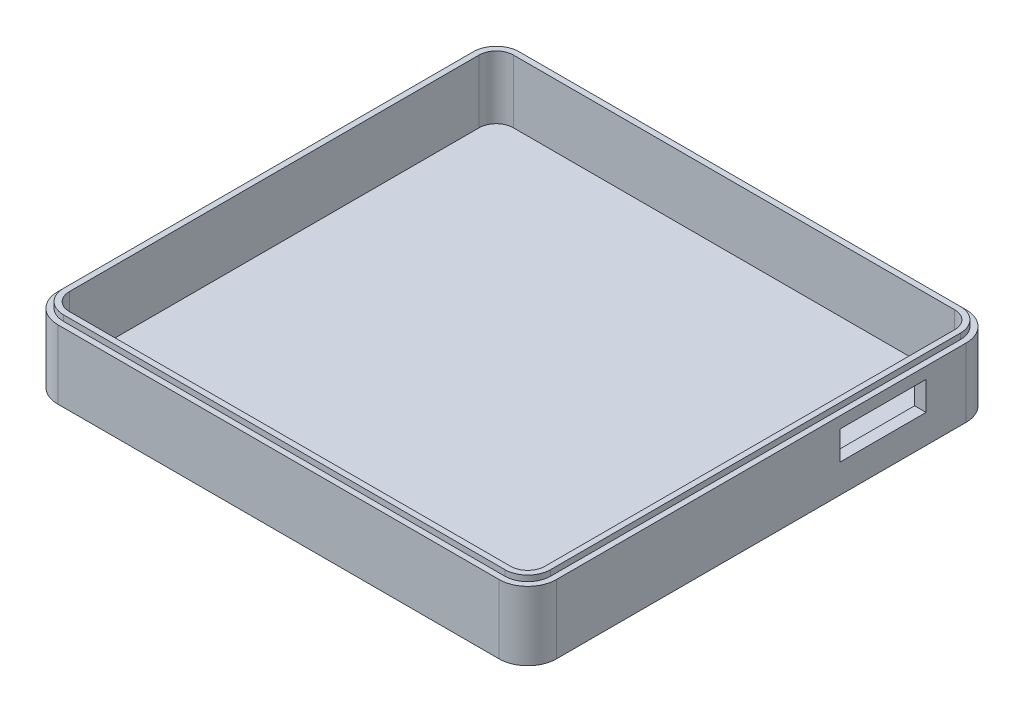
SolidWorks part; units mm, degrees
ref_plane "Спереди" through (0, 0, 0) normal (0, 0, 1) x (1, 0, 0)
ref_plane "Сверху" through (0, 0, 0) normal (0, 1, 0) x (1, 0, 0)
ref_plane "Справа" through (0, 0, 0) normal (1, 0, 0) x (0, 0, -1)
other "Configuration Table"
sketch "Эскиз1" plane through (0, 0, 0) normal (0, 1, 0) x (1, 0, 0)
  line L0 (41.4156, 1.5506) -> (41.4156, -75.9494)
  line L1 (2.9156, 1.5506) -> (79.9156, 1.5506) construction
  line L2 (-0.0844, -1.4494) -> (-0.0844, -72.9494) construction
  line L3 (2.9156, -75.9494) -> (79.9156, -75.9494) construction
  line L4 (82.9156, -1.4494) -> (82.9156, -72.9494) construction
  line L5 (-0.0844, -37.1994) -> (82.9156, -37.1994)
  line L6 (-2.0844, -1.4494) -> (-2.0844, -72.9494)
  line L7 (2.9156, -77.9494) -> (79.9156, -77.9494)
  line L8 (84.9156, -1.4494) -> (84.9156, -72.9494)
  line L9 (2.9156, 3.5506) -> (79.9156, 3.5506)
  line L10 (-0.0844, -1.4494) -> (-0.0844, -72.9494)
  line L11 (2.9156, -75.9494) -> (79.9156, -75.9494)
  line L12 (82.9156, -1.4494) -> (82.9156, -72.9494)
  line L13 (2.9156, 1.5506) -> (79.9156, 1.5506)
  circle A0 centre (9.9156, -65.9494) radius 3.9775
  circle A1 centre (9.9156, -8.4494) radius 3.9775
  circle A2 centre (72.9156, -8.4494) radius 3.9775
  circle A3 centre (72.9156, -65.9494) radius 3.9775
  arc A4 (79.9156, -75.9494) -> (82.9156, -72.9494) centre (79.9156, -72.9494) ccw construction
  arc A5 (79.9156, 1.5506) -> (82.9156, -1.4494) centre (79.9156, -1.4494) cw construction
  arc A6 (2.9156, 1.5506) -> (-0.0844, -1.4494) centre (2.9156, -1.4494) ccw construction
  arc A7 (-0.0844, -72.9494) -> (2.9156, -75.9494) centre (2.9156, -72.9494) ccw construction
  arc A8 (-2.0844, -72.9494) -> (2.9156, -77.9494) centre (2.9156, -72.9494) ccw
  arc A9 (79.9156, -77.9494) -> (84.9156, -72.9494) centre (79.9156, -72.9494) ccw
  arc A10 (79.9156, 3.5506) -> (84.9156, -1.4494) centre (79.9156, -1.4494) cw
  arc A11 (2.9156, 3.5506) -> (-2.0844, -1.4494) centre (2.9156, -1.4494) ccw
  arc A12 (-0.0844, -72.9494) -> (2.9156, -75.9494) centre (2.9156, -72.9494) ccw
  arc A13 (79.9156, -75.9494) -> (82.9156, -72.9494) centre (79.9156, -72.9494) ccw
  arc A14 (79.9156, 1.5506) -> (82.9156, -1.4494) centre (79.9156, -1.4494) cw
  arc A15 (2.9156, 1.5506) -> (-0.0844, -1.4494) centre (2.9156, -1.4494) ccw
  point P20 (82.9156, 1.5506)
  point P23 (-0.0844, 1.5506)
  point P26 (-0.0844, -75.9494)
  dimension "D3" = 10
  dimension "D5" = 3
  dimension "D1" = 83
  dimension "D2" = 77.5
  dimension "D4" = 10
extrude "Бобышка-Вытянуть4" add sketch "Эскиз1" along normal blind 2 contours L6 A8 L7 A9 L8 A10 L9 A11
extrude "Бобышка-Вытянуть5" add sketch "Эскиз1<9>" along normal blind 12 contours L6 A8 L7 A9 L8 A10 L9 A11 | L10 A12 L11 A13 L12 A14 L13 A15
sketch "Эскиз1<9>" plane through (0, 0, 0) normal (0, 1, 0) x (1, 0, 0) same geometry as "Эскиз1"
sketch "Эскиз3" plane through (0, 0, 0) normal (0, -1, 0) x (1, 0, 0)
  line L12 (2.9156, -2.5506) -> (79.9156, -2.5506)
  line L13 (83.9156, 1.4494) -> (83.9156, 72.9494)
  line L14 (79.9156, 76.9494) -> (2.9156, 76.9494)
  line L15 (-1.0844, 72.9494) -> (-1.0844, 1.4494)
  line L16 (2.9156, -2.5506) -> (79.9156, -2.5506)
  line L17 (83.9156, 1.4494) -> (83.9156, 72.9494)
  line L18 (79.9156, 76.9494) -> (2.9156, 76.9494)
  line L19 (-1.0844, 72.9494) -> (-1.0844, 1.4494)
  arc A12 (-1.0844, 1.4494) -> (2.9156, -2.5506) centre (2.9156, 1.4494) ccw
  arc A13 (79.9156, -2.5506) -> (83.9156, 1.4494) centre (79.9156, 1.4494) ccw
  arc A14 (83.9156, 72.9494) -> (79.9156, 76.9494) centre (79.9156, 72.9494) ccw
  arc A15 (2.9156, 76.9494) -> (-1.0844, 72.9494) centre (2.9156, 72.9494) ccw
  arc A16 (-1.0844, 1.4494) -> (2.9156, -2.5506) centre (2.9156, 1.4494) ccw
  arc A17 (79.9156, -2.5506) -> (83.9156, 1.4494) centre (79.9156, 1.4494) ccw
  arc A18 (83.9156, 72.9494) -> (79.9156, 76.9494) centre (79.9156, 72.9494) ccw
  arc A19 (2.9156, 76.9494) -> (-1.0844, 72.9494) centre (2.9156, 72.9494) ccw
  dimension "D1" = 1
extrude "Бобышка-Вытянуть7" add sketch "Эскиз3" against normal blind 1 from surface contours L18 A19 L19 A16 L16 A17 L17 A18 starting at face at (41.4156, 12, 37.1994)
extrude "Вырез-Вытянуть4" cut sketch "Эскиз1<13>" against normal blind 11 from surface contours L13 A14 L12 A13 L11 A12 L10 A15 starting at face at (41.4156, 13, 37.1994)
sketch "Эскиз1<13>" plane through (0, 0, 0) normal (0, 1, 0) x (1, 0, 0) same geometry as "Эскиз1"
sketch "Эскиз4" plane through (84.9156, 0, 0) normal (1, 0, 0) x (0, 0, -1)
  line L0 (-1.4494, 0) -> (-72.9494, 0) construction
  line L1 (-23.4494, 10) -> (-8.4494, 10)
  line L2 (-23.4494, 10) -> (-23.4494, 5)
  line L3 (-23.4494, 5) -> (-8.4494, 5)
  line L4 (-8.4494, 10) -> (-8.4494, 5)
  line L5 (-1.4494, 12) -> (-1.4494, 0) construction
  dimension "D1" = 15
  dimension "D2" = 5
  dimension "D3" = 5
  dimension "D4" = 7
extrude "Вырез-Вытянуть5" cut sketch "Эскиз4" against normal up to next
